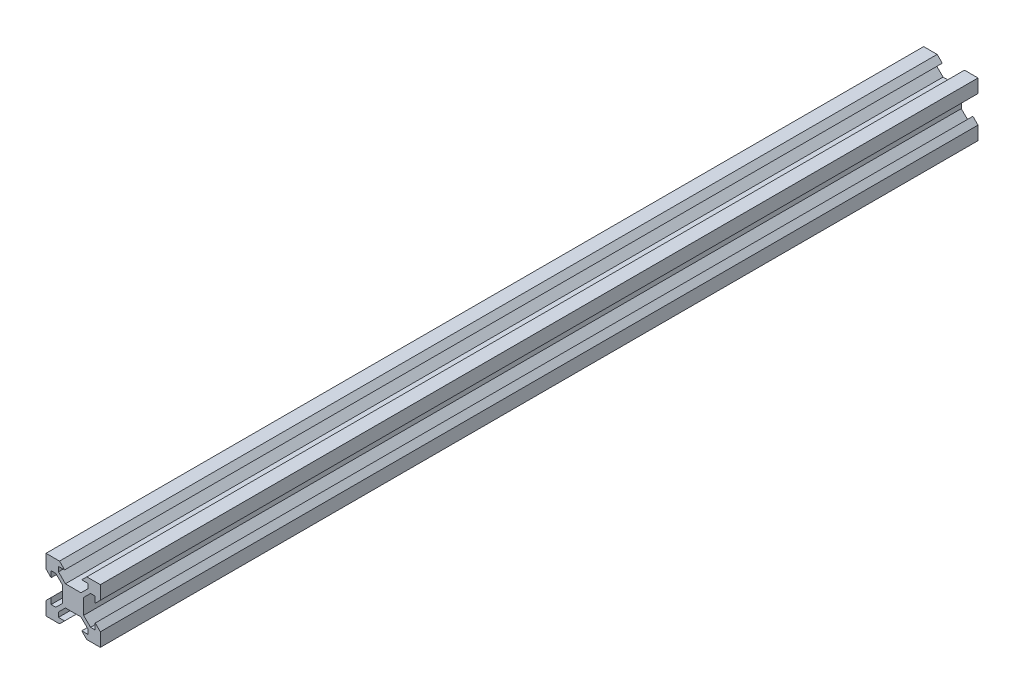
SolidWorks part; units mm, degrees
ref_plane "Front Plane" through (0, 0, 0) normal (0, 0, 1) x (1, 0, 0)
ref_plane "Top Plane" through (0, 0, 0) normal (0, 1, 0) x (1, 0, 0)
ref_plane "Right Plane" through (0, 0, 0) normal (1, 0, 0) x (0, 0, -1)
sketch "Sketch1" plane through (0, 0, 0) normal (0, 0, 1) x (1, 0, 0)
  line L0 (0, 0) -> (0, 10) construction
  line L1 (0, 0) -> (10, 0) construction
  line L2 (-2.8601, 3.85) -> (2.8601, 3.85)
  line L3 (5.4, 6.3899) -> (5.4, 8.125)
  line L4 (5.4, 8.125) -> (3.15, 8.125)
  line L5 (3.15, 8.125) -> (5.025, 10)
  line L6 (5.025, 10) -> (10, 10)
  line L7 (0, 0) -> (10, 10) construction
  line L8 (5.4, 6.3899) -> (2.8601, 3.85)
  line L9 (6.3899, 5.4) -> (3.85, 2.8601)
  line L10 (10, 5.025) -> (10, 10)
  line L11 (8.125, 3.15) -> (10, 5.025)
  line L12 (8.125, 5.4) -> (8.125, 3.15)
  line L13 (6.3899, 5.4) -> (8.125, 5.4)
  line L14 (3.85, -2.8601) -> (3.85, 2.8601)
  line L15 (6.3899, -5.4) -> (8.125, -5.4)
  line L16 (8.125, -5.4) -> (8.125, -3.15)
  line L17 (8.125, -3.15) -> (10, -5.025)
  line L18 (10, -5.025) -> (10, -10)
  line L19 (6.3899, -5.4) -> (3.85, -2.8601)
  line L20 (5.4, -6.3899) -> (2.8601, -3.85)
  line L21 (5.025, -10) -> (10, -10)
  line L22 (3.15, -8.125) -> (5.025, -10)
  line L23 (5.4, -8.125) -> (3.15, -8.125)
  line L24 (5.4, -6.3899) -> (5.4, -8.125)
  line L25 (-2.8601, -3.85) -> (2.8601, -3.85)
  line L26 (-5.4, -6.3899) -> (-5.4, -8.125)
  line L27 (-5.4, -8.125) -> (-3.15, -8.125)
  line L28 (-3.15, -8.125) -> (-5.025, -10)
  line L29 (-5.025, -10) -> (-10, -10)
  line L30 (-5.4, -6.3899) -> (-2.8601, -3.85)
  line L31 (-6.3899, -5.4) -> (-3.85, -2.8601)
  line L32 (-10, -5.025) -> (-10, -10)
  line L33 (-8.125, -3.15) -> (-10, -5.025)
  line L34 (-8.125, -5.4) -> (-8.125, -3.15)
  line L35 (-6.3899, -5.4) -> (-8.125, -5.4)
  line L36 (-3.85, -2.8601) -> (-3.85, 2.8601)
  line L37 (-6.3899, 5.4) -> (-8.125, 5.4)
  line L38 (-8.125, 5.4) -> (-8.125, 3.15)
  line L39 (-8.125, 3.15) -> (-10, 5.025)
  line L40 (-10, 5.025) -> (-10, 10)
  line L41 (-6.3899, 5.4) -> (-3.85, 2.8601)
  line L42 (-5.4, 6.3899) -> (-2.8601, 3.85)
  line L43 (-5.025, 10) -> (-10, 10)
  line L44 (-3.15, 8.125) -> (-5.025, 10)
  line L45 (-5.4, 8.125) -> (-3.15, 8.125)
  line L46 (-5.4, 6.3899) -> (-5.4, 8.125)
  point P19 (3.85, 0)
  point P31 (0, -3.85)
  point P32 (0, 3.85)
  point P52 (-3.85, 0)
  dimension "D1" = 10.8
  dimension "D2" = 6.15
  dimension "D4" = 10
  dimension "D5" = 1.4
  dimension "D6" = 6.3
  dimension "D7" = 45
  dimension "D8" = 16.25
extrude "Boss-Extrude1" add sketch "Sketch1" against normal blind 323
equation "\"length\"=323"
equation "\"D1@Boss-Extrude1\"=\"length\""
